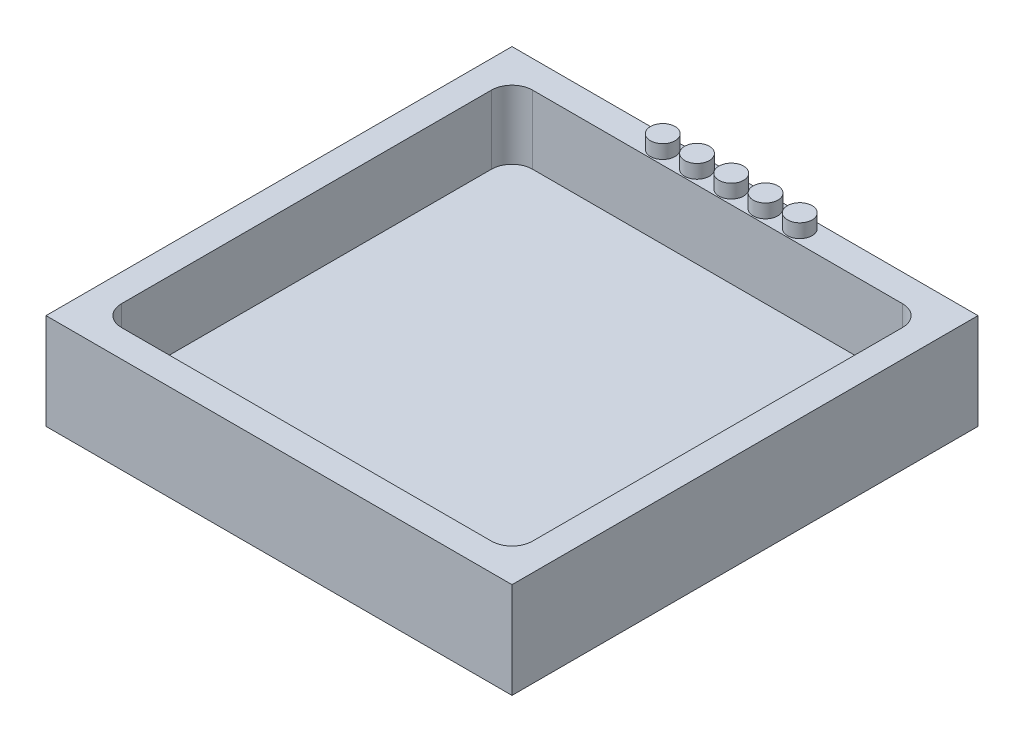
SolidWorks part; units mm, degrees
ref_plane "Front Plane" through (0, 0, 0) normal (0, 0, 1) x (1, 0, 0)
ref_plane "Top Plane" through (0, 0, 0) normal (0, 1, 0) x (1, 0, 0)
ref_plane "Right Plane" through (0, 0, 0) normal (1, 0, 0) x (0, 0, -1)
sketch "Sketch1" plane through (0, 0, 0) normal (0, 1, 0) x (1, 0, 0)
  line L1 (-15, -15) -> (15, -15)
  line L2 (-15, -15) -> (-15, 15)
  line L3 (-15, 15) -> (15, 15)
  line L4 (15, -15) -> (15, 15)
  line L5 (-15, -15) -> (15, 15) construction
  line L6 (-15, 15) -> (15, -15) construction
  line L7 (-17, -17) -> (17, -17)
  line L8 (-17, -17) -> (-17, 17)
  line L9 (-17, 17) -> (17, 17)
  line L10 (17, -17) -> (17, 17)
  line L11 (-17, -17) -> (17, 17) construction
  line L12 (-17, 17) -> (17, -17) construction
  point P0 (0, 0)
  point P6 (0, 0)
  dimension "D1" = 30
  dimension "D2" = 30
  dimension "D3" = 34
  dimension "D4" = 34
extrude "Boss-Extrude2" add sketch "Sketch1" along normal blind 2 contours L3 L4 L1 L2
extrude "Boss-Extrude3" add sketch "Sketch1<6>" along normal blind 7
sketch "Sketch1<6>" plane through (0, 0, 0) normal (0, 1, 0) x (1, 0, 0) same geometry as "Sketch1"
fillet "Fillet1" radius 1.5 4 edges at (15, 4.5, -15) (-15, 4.5, -15) (-15, 4.5, 15) (15, 4.5, 15)
sketch "Sketch2" plane through (0, 7, 0) normal (0, 1, 0) x (1, 0, 0)
  line L0 (0, -3.85) -> (0, 3.85) construction
  line L1 (-17, 17) -> (17, 17) construction
  circle A0 centre (0, 16) radius 0.9
  circle A1 centre (-2.5, 16) radius 0.9
  circle A2 centre (-5, 16) radius 0.9
  circle A3 centre (2.5, 16) radius 0.9
  circle A4 centre (5, 16) radius 0.9
  dimension "D1" = 1
  dimension "D2" = 2.5
  dimension "D3" = 2.5
  dimension "D4" = 2.5
  dimension "D5" = 2.5
extrude "Boss-Extrude4" add sketch "Sketch2" along normal blind 1
